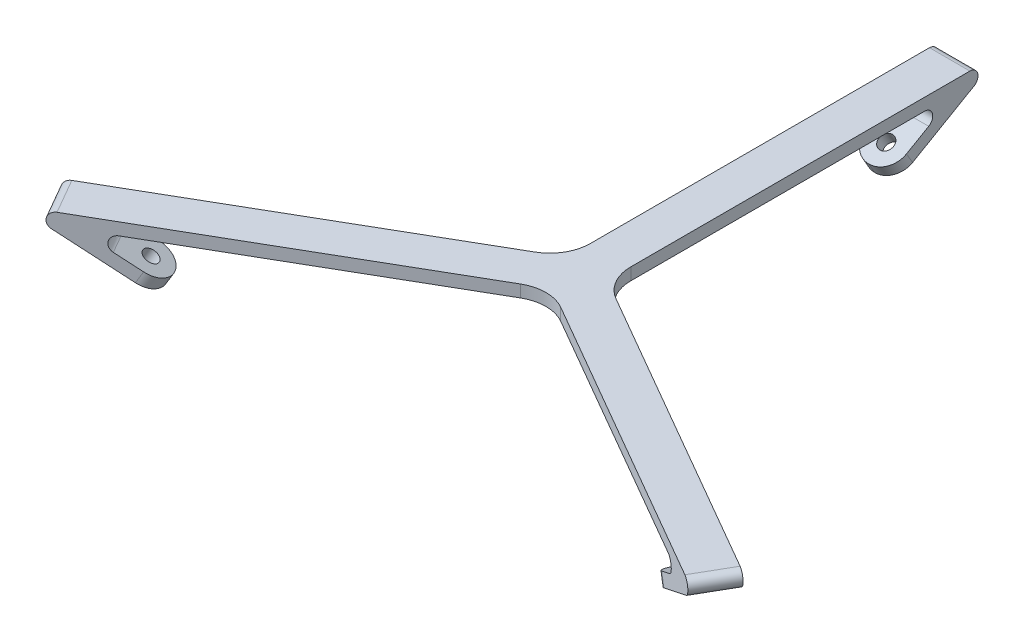
SolidWorks part; units mm, degrees
ref_plane "Front Plane" through (0, 0, 0) normal (0, 0, 1) x (1, 0, 0)
ref_plane "Top Plane" through (0, 0, 0) normal (0, 1, 0) x (1, 0, 0)
ref_plane "Right Plane" through (0, 0, 0) normal (1, 0, 0) x (0, 0, -1)
sketch "Sketch2" plane through (0, 0, 0) normal (0, 1, 0) x (1, 0, 0)
  line L0 (0, 0) -> (-5, 2.8868)
  line L4 (-5, 2.8868) -> (-5, 100)
  line L5 (-5, 100) -> (5, 100)
  line L6 (5, 100) -> (5, 2.8868)
  line L7 (5, 2.8868) -> (0, 0)
  line L8 (0, 0) -> (0, 124.9609) construction
  dimension "D1" = 120
  dimension "D2" = 60
  dimension "D3" = 10
  dimension "D4" = 100
extrude "Boss-Extrude1" add sketch "Sketch2" along normal blind 15
sketch "Sketch3" plane through (5, 0, 0) normal (1, 0, 0) x (0, 0, -1)
  line L8 (0, 12) -> (88.8038, 12)
  line L10 (88.8038, 12) -> (68.0192, 0)
  line L11 (2.8868, 0) -> (100, 0) construction
  line L12 (68.0192, 0) -> (0, 0)
  line L13 (0, 0) -> (0, 12)
  line L14 (100, 15) -> (74.0192, 0)
  line L15 (74.0192, 0) -> (100, 0)
  line L16 (100, 0) -> (100, 15)
  dimension "D1" = 3
  dimension "D2" = 30
  dimension "D3" = 12
extrude "Cut-Extrude1" cut sketch "Sketch3" against normal up to next
sketch "Sketch4" plane through (0, -32.0513, -18.5048) normal (0, -0.866, -0.5) x (1, 0, 0)
  line L0 (-5, -64.1025) -> (5, -64.1025) construction
  line L2 (-5, -64.1025) -> (-5, -94.1025) construction
  circle A0 centre (0, -69.1025) radius 1.7
  point P0 (0, -69.1025)
  dimension "D1" = 3.4
  dimension "D2" = 5
  dimension "D3" = 5
hole_wizard "M3 Clearance Hole1" positions "Sketch4" profile "Sketch5" hole size "M3" standard "ANSI Metric"
sketch "Sketch5" plane through (0, 2.5, -78.3494) normal (1, 0, 0) x (0, 0.5, -0.866)
  line L0 (0, 0) -> (0, 3)
  line L1 (0, 3) -> (1.8, 3)
  line L2 (1.8, 3) -> (1.8, 0)
  line L5 (1.8, 0) -> (0, 0)
  line L11 (0, -6.35) -> (0, 107.95) construction
  dimension "Thru Hole Dia." = 3.6
  dimension "Thru Hole Depth" = 3
sketch "Sketch6" plane through (5, 0, 0) normal (1, 0, 0) x (0, 0, -1)
  line L0 (74.0192, 0) -> (68.0192, 0)
  line L1 (68.0192, 0) -> (72.5192, 2.5981)
  line L2 (68.0192, 0) -> (88.8038, 12) construction
  line L3 (72.5192, 2.5981) -> (74.0192, 0)
  dimension "D1" = 90
extrude "Cut-Extrude2" cut sketch "Sketch6" against normal up to next
pattern_circular "CirPattern1" count 3 every 120 about axis through (0, 0, 0) along (0, 1, 0) of "Boss-Extrude1", "M3 Clearance Hole1", "Cut-Extrude1", "Cut-Extrude2"
fillet "Fillet1" radius 2 6 edges at (76.9064, 12, 44.4019) (-76.9064, 12, 44.4019) (0, 15, -100) (0, 12, -88.8038) (-86.6025, 15, 50) (86.6025, 15, 50)
fillet "Fillet2" radius 10 3 edges at (5, 13.5, -2.8868) (-5, 13.5, -2.8868) (0, 13.5, 5.7735)
fillet "Fillet3" radius 5 6 edges at (65.953, 1.299, 32.3045) (60.953, 1.299, 40.9647) (-60.953, 1.299, 40.9647) (-65.953, 1.299, 32.3045) (-5, 1.299, -73.2692) (5, 1.299, -73.2692)
